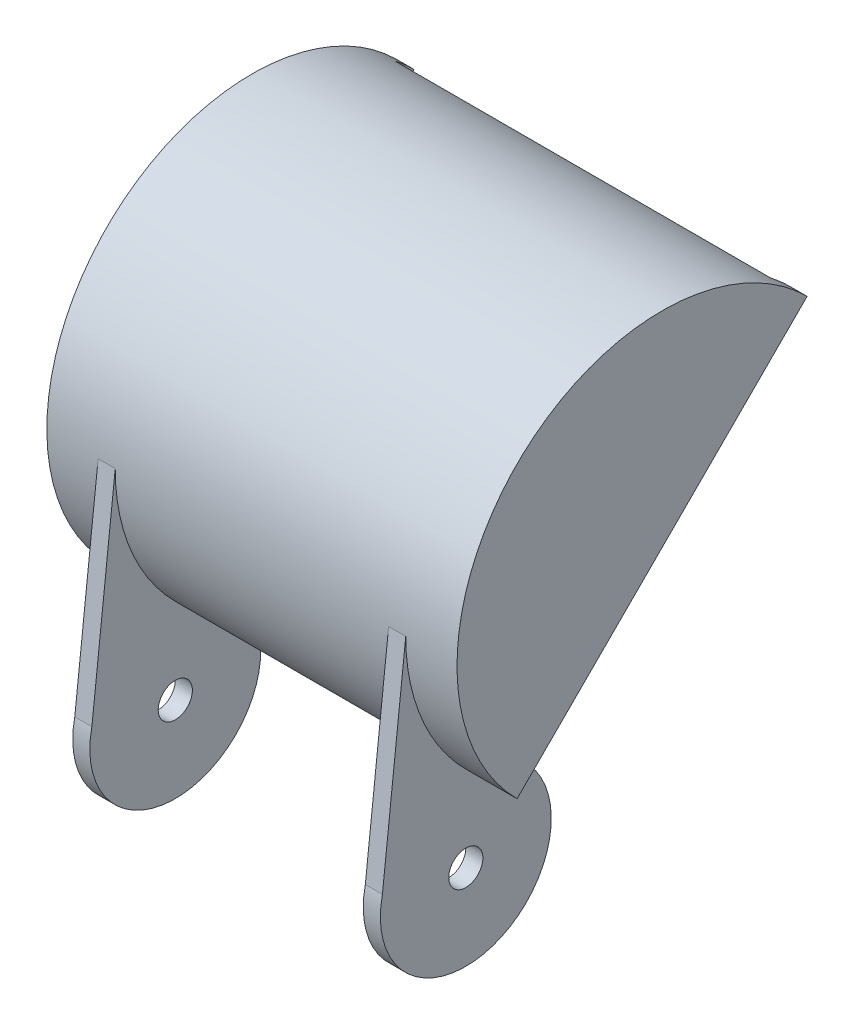
SolidWorks part; units mm, degrees
material "6061-T6 (SS)"
ref_plane "Front Plane" through (0, 0, 0) normal (0, 0, 1) x (1, 0, 0)
ref_plane "Top Plane" through (0, 0, 0) normal (0, 1, 0) x (1, 0, 0)
ref_plane "Right Plane" through (0, 0, 0) normal (1, 0, 0) x (0, 0, -1)
sketch "ExcavatorReferenceSize" plane through (0, 0, 0) normal (0, 1, 0) x (1, 0, 0)
  line L1 (-25.4, -12.7) -> (25.4, -12.7)
  line L2 (-25.4, -12.7) -> (-25.4, 12.7)
  line L3 (-25.4, 12.7) -> (25.4, 12.7)
  line L4 (25.4, -12.7) -> (25.4, 12.7)
  line L5 (-25.4, -12.7) -> (25.4, 12.7) construction
  line L6 (-25.4, 12.7) -> (25.4, -12.7) construction
  point P0 (0, 0)
  dimension "D1" = 25.4
  dimension "D2" = 50.8
sketch "Sketch2" plane through (0, 0, 0) normal (1, 0, 0) x (0, 0, -1)
  line L0 (0, 0) -> (53.8815, 53.8815)
  line L1 (0, 0) -> (0, -12.7) construction
  arc A0 (53.8815, 53.8815) -> (0, 0) centre (26.9408, 26.9408) ccw
  dimension "D1" = 76.2
  dimension "D2" = 12.7
extrude "Boss-Extrude1" add sketch "Sketch2" along normal mid plane 76.2
shell "Shell1" thickness 3.175 removed face at (0, 26.9408, -26.9408)
chamfer "Chamfer1" distance 10 angle 45 1 edges at (0, 51.6365, -51.6365)
sketch "Sketch4" plane through (0, 0, 0) normal (1, 0, 0) x (0, 0, -1)
  circle A1 centre (0, -15.875) radius 15.875
  dimension "D1" = 31.75
extrude "Boss-Extrude3" add sketch "Sketch4" along normal mid plane 57.15
sketch "Sketch5" plane through (0, 0, 0) normal (1, 0, 0) x (0, 0, -1)
  line L0 (2.2451, 2.2451) -> (2.2451, -0.1596)
  line L1 (2.2451, 2.2451) -> (0, 0)
  line L2 (0, 0) -> (2.2451, -0.1596)
  circle A0 centre (0, -15.875) radius 15.875 construction
  circle A1 centre (0, -15.875) radius 15.875 construction
  dimension "D1" = 3.175
extrude "Boss-Extrude4" add sketch "Sketch5" along normal mid plane 57.15
sketch "Sketch6" plane through (0, 0, 0) normal (1, 0, 0) x (0, 0, -1)
  line L0 (0, 0) -> (0, -15.875) construction
  circle A1 centre (0, -15.875) radius 15.875
extrude "Cut-Extrude2" cut sketch "Sketch6" against normal blind 25.4
extrude "Cut-Extrude3" cut sketch "Sketch6<2>" along normal blind 25.4
sketch "Sketch6<2>" plane through (0, 0, 0) normal (1, 0, 0) x (0, 0, -1) same geometry as "Sketch6"
sketch "Sketch7" plane through (-28.575, 0, 0) normal (-1, 0, 0) x (0, 0, 1)
  line L0 (0, 0) -> (0, -15.875) construction
  circle A0 centre (0, -15.875) radius 3.175
  dimension "D1" = 15.875
extrude "Cut-Extrude4" cut sketch "Sketch7" against normal up to surface (57.15 mm away) up to face at (28.575, -9.8483, -0.7474)
sketch "Sketch8" plane through (28.575, 0, 0) normal (1, 0, 0) x (0, 0, -1)
  line L0 (-11.1592, 26.9408) -> (-15.875, -15.875)
  line L2 (2.2451, 2.2451) -> (-15.875, -15.875)
  line L3 (-11.1592, 26.9408) -> (2.2451, 2.2451) construction
  line L4 (-11.1592, 26.9408) -> (-7.223, 19.6888)
  arc A0 (53.8815, 53.8815) -> (0, 0) centre (26.9408, 26.9408) ccw construction
  arc A1 (53.8815, 53.8815) -> (0, 0) centre (26.9408, 26.9408) ccw construction
  circle A2 centre (0, -15.875) radius 15.875 construction
  arc A3 (45.5198, 56.514) -> (2.2451, 2.2451) centre (26.9408, 26.9408) ccw
  arc A4 (-7.223, 19.6888) -> (2.2451, 2.2451) centre (26.9408, 26.9408) ccw
  point P11 (-7.223, 19.6888)
extrude "Boss-Extrude5" add sketch "Sketch8" against normal up to surface (57.15 mm away) up to face at (-28.575, -15.875, 3.175)
ref_plane "Plane1" through (0, -15.875, 0) normal (0, 1, 0) x (1, 0, 0)
sketch "Sketch9" plane through (0, 0, 0) normal (1, 0, 0) x (0, 0, -1)
  line L3 (2.2451, -0.1596) -> (2.2451, 2.2451)
  line L4 (2.2451, 2.2451) -> (0, 0)
  line L5 (-11.1592, 26.9408) -> (-15.4945, -12.4199)
  line L6 (2.2451, -0.1596) -> (2.2451, 2.2451)
  line L7 (2.2451, 2.2451) -> (0, 0)
  line L8 (-11.1592, 26.9408) -> (-15.4945, -12.4199)
  arc A2 (-15.4945, -12.4199) -> (2.2451, -0.1596) centre (0, -15.875) ccw
  arc A3 (-11.1592, 26.9408) -> (0, 0) centre (26.9408, 26.9408) ccw
  arc A4 (-15.4945, -12.4199) -> (2.2451, -0.1596) centre (0, -15.875) ccw
  arc A5 (-11.1592, 26.9408) -> (0, 0) centre (26.9408, 26.9408) ccw
  dimension "D1" = 0
extrude "Cut-Extrude5" cut sketch "Sketch9" against normal mid plane 50.8
sketch "Sketch11" plane through (0, 0, 0) normal (1, 0, 0) x (0, 0, -1)
  line L2 (63.8276, 60.2315) -> (53.8815, 53.8815)
  line L6 (30.5368, 61.8712) -> (30.5368, 53.8815) construction
  line L7 (53.8815, 53.8815) -> (30.5368, 53.8815) construction
  line L8 (53.8815, 53.8815) -> (53.8815, 60.2315) construction
  line L9 (53.8815, 60.2315) -> (41.5936, 60.2315)
  line L10 (53.8815, 60.2315) -> (63.8276, 60.2315)
  circle A0 centre (0, -15.875) radius 3.175 construction
  circle A1 centre (0, -15.875) radius 3.175 construction
  arc A3 (53.8815, 53.8815) -> (41.5936, 60.2315) centre (30.5368, 23.7712) ccw
  point P3 (0, 0)
  point P8 (0, 0)
  dimension "D1" = 6.35
  dimension "D2" = 76.2
extrude "Boss-Extrude6" [suppressed] add sketch "Sketch11" along normal mid plane 6.35
pattern_linear "LPattern1" [suppressed] count 2 spacing 28.575 of bodies 111
pattern_linear "LPattern2" [suppressed] count 2 spacing 28.575 of bodies 112
ref_plane "Plane2" [suppressed] through (0, 51.6365, -51.6365) normal (0, -0.7071, 0.7071) x (-1, 0, 0)
sketch "Sketch13" [suppressed] plane through (0, 51.6365, -51.6365) normal (0, -0.7071, 0.7071) x (-1, 0, 0)
  line L0 (31.75, 0) -> (31.75, -10.4379) construction
  line L1 (31.75, -10.4379) -> (25.4, -10.4379) construction
  line L2 (25.4, -10.4379) -> (25.4, 0) construction
  line L3 (25.4, 0) -> (31.75, 0) construction
  line L4 (3.175, 0) -> (3.175, -10.4379) construction
  line L5 (3.175, -10.4379) -> (-3.175, -10.4379) construction
  line L6 (-3.175, -10.4379) -> (-3.175, 0) construction
  line L7 (-3.175, 0) -> (3.175, 0) construction
  line L8 (-25.4, 0) -> (-25.4, -10.4379) construction
  line L9 (-25.4, -10.4379) -> (-31.75, -10.4379) construction
  line L10 (-31.75, -10.4379) -> (-31.75, 0) construction
  line L11 (-31.75, 0) -> (-25.4, 0) construction
  line L12 (31.75, 0) -> (31.75, -10.4379) construction
  line L13 (31.75, -10.4379) -> (25.4, -10.4379) construction
  line L14 (25.4, -10.4379) -> (25.4, 0) construction
  line L15 (25.4, 0) -> (31.75, 0) construction
  line L16 (3.175, 0) -> (3.175, -10.4379) construction
  line L17 (3.175, -10.4379) -> (-3.175, -10.4379) construction
  line L18 (-3.175, -10.4379) -> (-3.175, 0) construction
  line L19 (-3.175, 0) -> (3.175, 0) construction
  line L20 (-25.4, 0) -> (-25.4, -10.4379) construction
  line L21 (-25.4, -10.4379) -> (-31.75, -10.4379) construction
  line L22 (-31.75, -10.4379) -> (-31.75, 0) construction
  line L23 (-31.75, 0) -> (-25.4, 0) construction
  circle A0 centre (-28.575, -5.219) radius 0.8954
  circle A1 centre (0, -5.219) radius 1.2111
  circle A2 centre (28.575, -5.219) radius 1.0326
  point P6 (-28.575, -10.4379)
  point P7 (-25.4, -5.219)
  point P18 (0, -10.4379)
  point P20 (28.575, -10.4379)
extrude "Cut-Extrude6" [suppressed] cut sketch "Sketch13" along normal up to surface and the other way up to surface up to face at (0, 20.6462, -7.0018)
